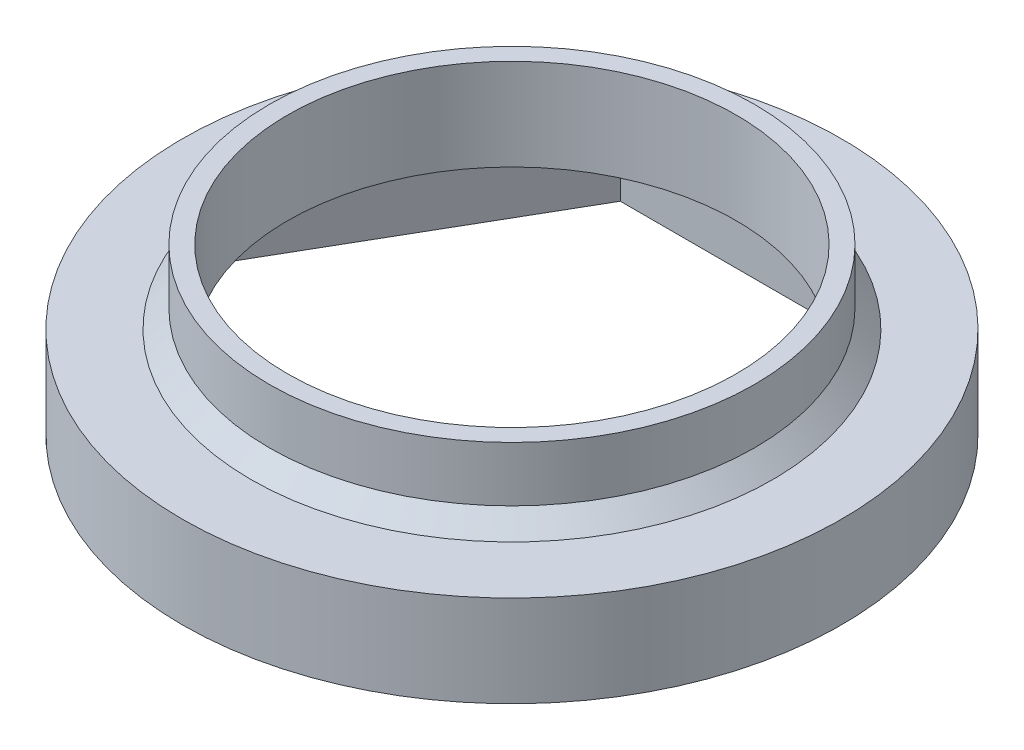
SolidWorks part; units mm, degrees
ref_plane "Front Plane" through (0, 0, 0) normal (0, 0, 1) x (1, 0, 0)
ref_plane "Top Plane" through (0, 0, 0) normal (0, 1, 0) x (1, 0, 0)
ref_plane "Right Plane" through (0, 0, 0) normal (1, 0, 0) x (0, 0, -1)
sketch "Sketch1" plane through (0, 0, 0) normal (0, 1, 0) x (1, 0, 0)
  line L7 (8.0829, -14) -> (16.1658, 0)
  line L8 (16.1658, 0) -> (8.0829, 14)
  line L9 (8.0829, 14) -> (-8.0829, 14)
  line L10 (-8.0829, 14) -> (-16.1658, 0)
  line L11 (-16.1658, 0) -> (-8.0829, -14)
  line L12 (-8.0829, -14) -> (8.0829, -14)
  circle A0 centre (0, 0) radius 14 construction
  circle A1 centre (0, 0) radius 18
  dimension "D2" = 36
  dimension "D1" = 28
extrude "Boss-Extrude1" add sketch "Sketch1" along normal blind 4
sketch "Sketch2" plane through (0, 4, 0) normal (0, 1, 0) x (1, 0, 0)
  circle A0 centre (0, 0) radius 12.25
  circle A1 centre (0, 0) radius 13.25
  dimension "D1" = 24.5
  dimension "D2" = 26.5
extrude "Boss-Extrude2" add sketch "Sketch2" along normal blind 5 separate body
sketch "Sketch3" plane through (0, 4, 0) normal (0, 1, 0) x (1, 0, 0)
  circle A0 centre (0, 0) radius 18 construction
  circle A1 centre (0, 0) radius 18
  circle A2 centre (0, 0) radius 12.25 construction
  circle A3 centre (0, 0) radius 12.25
extrude "Boss-Extrude3" add sketch "Sketch3" along normal blind 1
chamfer "Chamfer1" distance 1 angle 45 1 edges at (0, 5, 13.25)
